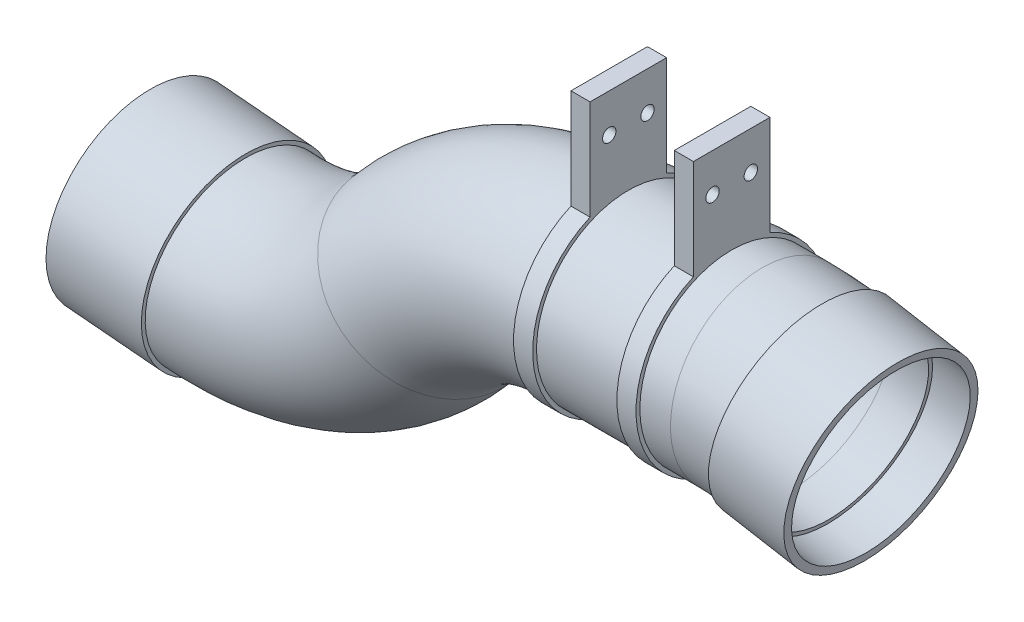
SolidWorks part; units mm, degrees
ref_plane "前视基准面" through (0, 0, 0) normal (0, 0, 1) x (1, 0, 0)
ref_plane "上视基准面" through (0, 0, 0) normal (0, 1, 0) x (1, 0, 0)
ref_plane "右视基准面" through (0, 0, 0) normal (1, 0, 0) x (0, 0, -1)
sketch "草图7" plane through (0, 0, 0) normal (0, 1, 0) x (1, 0, 0)
  line L0 (0, 0) -> (0, -51.07)
ref_plane "基准面2" through (0, 0, 0) normal (0.9962, -0.0872, 0) x (0, 0, 1)
sketch "草图2" plane through (0, 0, 0) normal (0, 0, 1) x (1, 0, 0)
  line L0 (9.9619, -0.8716) -> (15.1913, 58.9001) construction
  line L1 (15.1913, 58.9001) -> (61.154, 20.3329) construction
  line L2 (0, 0) -> (21.513, 0) construction
  line L3 (107.1166, 41.7656) -> (107.1166, -18.2344) construction
  line L4 (107.1166, 41.7656) -> (147.1166, 41.7656)
  line L5 (147.1166, 41.7656) -> (147.1166, -23.2344) construction
  line L6 (147.1166, -23.2344) -> (158.4038, 40.7781) construction
  line L7 (0, 0) -> (9.9619, -0.8716)
  line L9 (158.4038, 40.7781) -> (168.2518, 39.0416)
  line L12 (61.154, 20.3329) -> (107.1166, -18.2344) construction
  arc A1 (147.1166, 41.7656) -> (158.4038, 40.7781) centre (147.1166, -23.2344) cw
  arc A2 (9.9619, -0.8716) -> (61.154, 20.3329) centre (15.1913, 58.9001) ccw
  arc A3 (61.154, 20.3329) -> (107.1166, 41.7656) centre (107.1166, -18.2344) cw
  point P7 (0, 0)
  dimension "D2" = 60
  dimension "D3" = 55
  dimension "D5" = 40
  dimension "D6" = 65
  dimension "D13" = 60
  dimension "D4" = 5
  dimension "D7" = 10
  dimension "D8" = 10
  dimension "D9" = 10
sketch "草图1" plane through (0, 0, 0) normal (0.9962, -0.0872, 0) x (-0.0872, -0.9962, 0)
  circle A0 centre (0, 0) radius 22
  circle A1 centre (0, 0) radius 24
  dimension "D1" = 44
  dimension "D2" = 48
sweep "扫描1" add profiles "草图1" path "草图2"
sketch "草图3" plane through (0, 0, 0) normal (-0.9962, 0.0872, 0) x (-0.0872, -0.9962, 0)
  circle A0 centre (0, 0) radius 23
  circle A1 centre (0, 0) radius 25
  dimension "D1" = 46
  dimension "D2" = 50
extrude "凸台-拉伸1" add sketch "草图3" along normal blind 15 and the other way blind 10 separate body
sketch "草图4" plane through (156.5019, -27.5955, 0) normal (-0.9848, 0.1736, 0) x (0.1736, 0.9848, 0)
  circle A0 centre (67.6651, 0) radius 23
  circle A1 centre (67.6651, 0) radius 25
  circle A4 centre (67.6651, 0) radius 22 construction
  dimension "D1" = 46
  dimension "D2" = 50
extrude "凸台-拉伸2" add sketch "草图4" along normal blind 10 and the other way blind 10
ref_plane "基准面4" through (107.1166, 0, 0) normal (1, 0, 0) x (0, 0, -1)
sketch "草图12" plane through (107.1166, 0, -146.4509) normal (-1, 0, 0) x (0, 0, 1)
  line L0 (136.4509, 64.6785) -> (136.4509, 90.7656)
  line L8 (156.4509, 90.7656) -> (136.4509, 90.7656)
  line L9 (156.4509, 64.6785) -> (156.4509, 90.7656)
  line L10 (146.4509, 90.7656) -> (146.4509, 41.7656) construction
  line L11 (181.3782, 65.7656) -> (121.1251, 65.7656) construction
  arc A0 (136.4509, 64.6785) -> (156.4509, 64.6785) centre (146.4509, 41.7656) ccw
  circle A1 centre (146.4509, 41.7656) radius 24 construction
  circle A2 centre (146.4509, 41.7656) radius 24
  dimension "D3" = 50
  dimension "D1" = 20
  dimension "D2" = 25
extrude "凸台-拉伸4" add sketch "草图12" against normal blind 5
sketch "草图16" plane through (112.1166, 0, 0) normal (1, 0, 0) x (0, 0, -1)
  line L0 (-10, 90.7656) -> (10, 90.7656) construction
  line L1 (-5, 80.7656) -> (5, 80.7656) construction
  line L2 (0, 90.7656) -> (0, 80.7656) construction
  circle A2 centre (-5, 80.7656) radius 1.75
  circle A3 centre (5, 80.7656) radius 1.75
  dimension "D2" = 10
  dimension "D1" = 3.5
  dimension "D3" = 10
extrude "切除-拉伸1" cut sketch "草图16" against normal up to surface (5 mm away) up to face at (107.1166, 65.7656, 0)
pattern_linear "阵列(线性)1" count 2 spacing 27 along (1, 0, 0) of "凸台-拉伸4", "切除-拉伸1"
